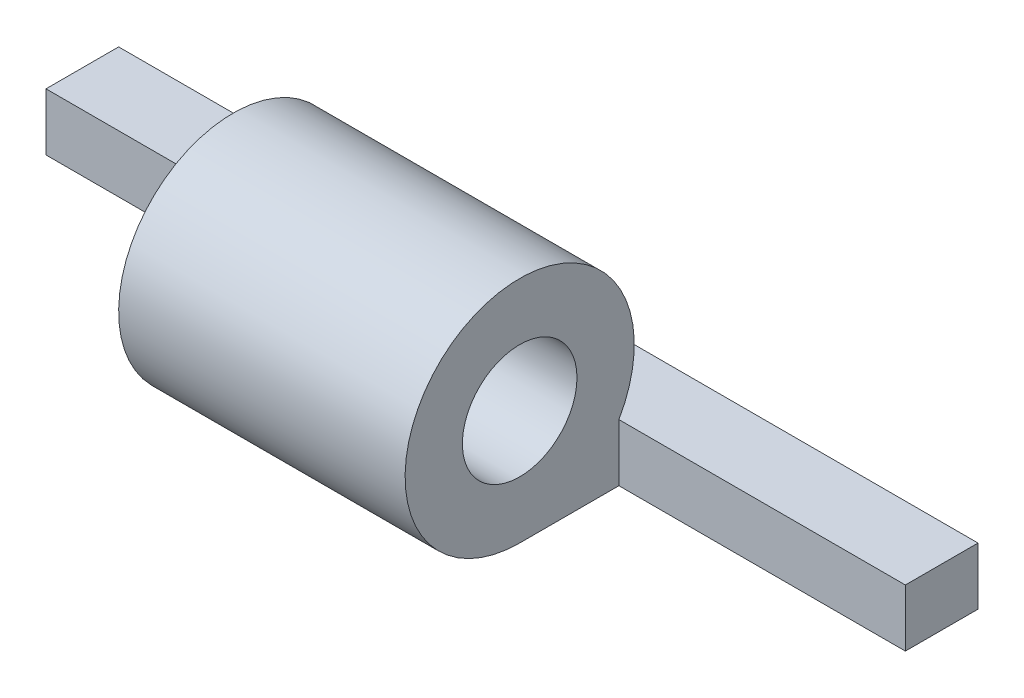
SolidWorks part; units mm, degrees
ref_plane "Ebene vorne" through (0, 0, 0) normal (0, 0, 1) x (1, 0, 0)
ref_plane "Ebene oben" through (0, 0, 0) normal (0, 1, 0) x (1, 0, 0)
ref_plane "Ebene rechts" through (0, 0, 0) normal (1, 0, 0) x (0, 0, -1)
sketch "Skizze1" plane through (0, 0, 0) normal (0, 1, 0) x (1, 0, 0)
  line L1 (0, 0) -> (15, 0)
  line L2 (0, 0) -> (0, 3)
  line L3 (0, 3) -> (15, 3)
  line L4 (15, 0) -> (15, 3)
  dimension "D1" = 15
  dimension "D2" = 3
extrude "Aufsatz-Linear austragen1" add sketch "Skizze1" along normal blind 1
sketch "Skizze2" plane through (15, 0, 0) normal (1, 0, 0) x (0, 0, -1)
  circle A0 centre (0, 2) radius 2
  circle A1 centre (0, 2) radius 1
  dimension "D1" = 2
  dimension "D2" = 1
extrude "Aufsatz-Linear austragen2" add sketch "Skizze2" against normal up to surface (15 mm away) up to face at (0, 0.5, -1.5)
ref_plane "Tangential Ebene" through (0, 0, -2) normal (0, 0, -1) x (-1, 0, 0)
sketch "Skizze8" plane through (15, 0, 0) normal (1, 0, 0) x (0, 0, -1)
  line L0 (1.7321, 1) -> (1.7321, 0)
  line L1 (1.7321, 0) -> (0, 0)
  line L3 (0, 0) -> (3, 0)
  line L4 (3, 0) -> (3, 1)
  line L5 (3, 1) -> (1.7321, 1)
  line L6 (0, 0) -> (3, 0) construction
  line L7 (3, 0) -> (3, 1) construction
  line L8 (3, 1) -> (1.7321, 1) construction
  arc A1 (1.7321, 1) -> (0, 0) centre (0, 2) ccw
  arc A2 (1.7321, 1) -> (0, 0) centre (0, 2) ccw
  dimension "D1" = 0
extrude "Schnitt-Linear austragen1" cut sketch "Skizze8" against normal blind 5
pattern_linear "Lineares Muster1" count 3 spacing 5 along (-1, 0, 0) skipping (1, 0) of "Schnitt-Linear austragen1"
